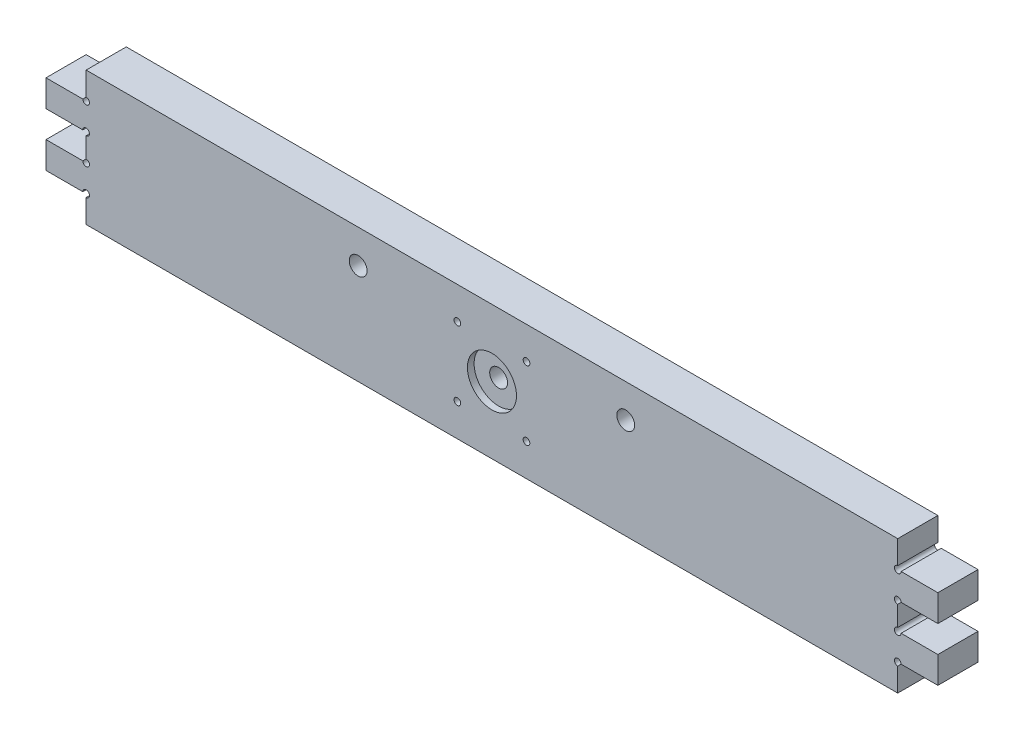
SolidWorks part; units mm, degrees
ref_plane "Front Plane" through (0, 0, 0) normal (0, 0, 1) x (1, 0, 0)
ref_plane "Top Plane" through (0, 0, 0) normal (0, 1, 0) x (1, 0, 0)
ref_plane "Right Plane" through (0, 0, 0) normal (1, 0, 0) x (0, 0, -1)
sketch "Sketch1" plane through (0, 0, 0) normal (0, 0, 1) x (1, 0, 0)
  line L0 (0, -1000) -> (0, 49000) construction
  line L1 (-182, -30) -> (182, -30)
  line L2 (-200, -18) -> (-200, -6)
  line L3 (-182, 30) -> (182, 30)
  line L4 (200, -18) -> (200, -6)
  line L5 (-182, -19.5) -> (-182, -30)
  line L6 (-200, -18) -> (-183.5, -18)
  line L7 (-1000, 0) -> (49000, 0) construction
  line L8 (182, 30) -> (182, 19.5)
  line L9 (200, 18) -> (183.5, 18)
  line L10 (200, 6) -> (183.5, 6)
  line L11 (200, -6) -> (183.5, -6)
  line L12 (200, -18) -> (183.5, -18)
  line L13 (182, 4.5) -> (182, -4.5)
  line L14 (200, 6) -> (200, 18)
  line L15 (200, -30) -> (182, -30) [skipped]
  line L16 (182, -19.5) -> (182, -30)
  line L17 (-200, -6) -> (-183.5, -6)
  line L18 (-182, 4.5) -> (-182, -4.5)
  line L19 (-200, 6) -> (-183.5, 6)
  line L20 (-182, 30) -> (-182, 19.5)
  line L21 (-200, 18) -> (-183.5, 18)
  line L22 (-200, 18) -> (-200, 6)
  line L23 (-200, 6) -> (-200, 18)
  line L24 (-200, -6) -> (-200, -18)
  line L25 (-1145.7551, 15) -> (48854.2449, 15) construction
  circle A0 centre (0, 0) radius 4
  circle A1 centre (60, 15) radius 4
  circle A2 centre (-60, 15) radius 4
  arc A3 (182, 19.5) -> (183.5, 18) centre (182, 18) ccw
  arc A4 (183.5, 6) -> (182, 4.5) centre (182, 6) ccw
  arc A5 (182, -4.5) -> (183.5, -6) centre (182, -6) ccw
  arc A6 (183.5, -18) -> (182, -19.5) centre (182, -18) ccw
  arc A7 (-183.5, 18) -> (-182, 19.5) centre (-182, 18) ccw
  arc A8 (-182, 4.5) -> (-183.5, 6) centre (-182, 6) ccw
  arc A9 (-183.5, -6) -> (-182, -4.5) centre (-182, -6) ccw
  arc A10 (-182, -19.5) -> (-183.5, -18) centre (-182, -18) ccw
  point P0 (0, 0)
  point P20 (182, 0)
  point P52 (0, 0)
  point P54 (0, 0)
  point P55 (0, 0)
  point P56 (0, 0)
  dimension "D7" = 8
  dimension "D8" = 8
  dimension "D9" = 8
  dimension "D10" = 60
  dimension "D11" = 60
  dimension "D4" = 3
  dimension "D15" = 3
  dimension "D2" = 60
  dimension "D3" = 18
  dimension "D6" = 400
  dimension "D13" = 18
  dimension "D14" = 16.5
  dimension "D17" = 15
  dimension "D5" = 5
  dimension "D12" = 4
  dimension "D16" = 4
extrude "Boss-Extrude1" add sketch "Sketch1" along normal blind 18 contours L21 L22 L19 L18 L17 L2 L6 L5 L1 L16 L12 L4 L11 L13 L10 L14 L9 L8 L3 L20 A2 A1 A0 region at (-177.9553, -24.75, 0)
sketch "Sketch2" plane through (0, 0, 18) normal (0, 0, 1) x (1, 0, 0)
  line L0 (-1000, 0) -> (49000, 0) construction
  line L1 (0, -1000) -> (0, 49000) construction
  circle A0 centre (15.495, 15.495) radius 1.5
  circle A4 centre (-15.495, 15.495) radius 1.5
  circle A5 centre (15.495, -15.495) radius 1.5
  circle A6 centre (-15.495, -15.495) radius 1.5
  dimension "D1" = 3
  dimension "D2" = 15.495
  dimension "D3" = 15.495
extrude "Cut-Extrude1" cut sketch "Sketch2" against normal up to next
sketch "Sketch3" plane through (0, 0, 18) normal (0, 0, 1) x (1, 0, 0)
  circle A0 centre (0, 0) radius 11
  dimension "D1" = 22
extrude "Cut-Extrude2" cut sketch "Sketch3" against normal blind 3
